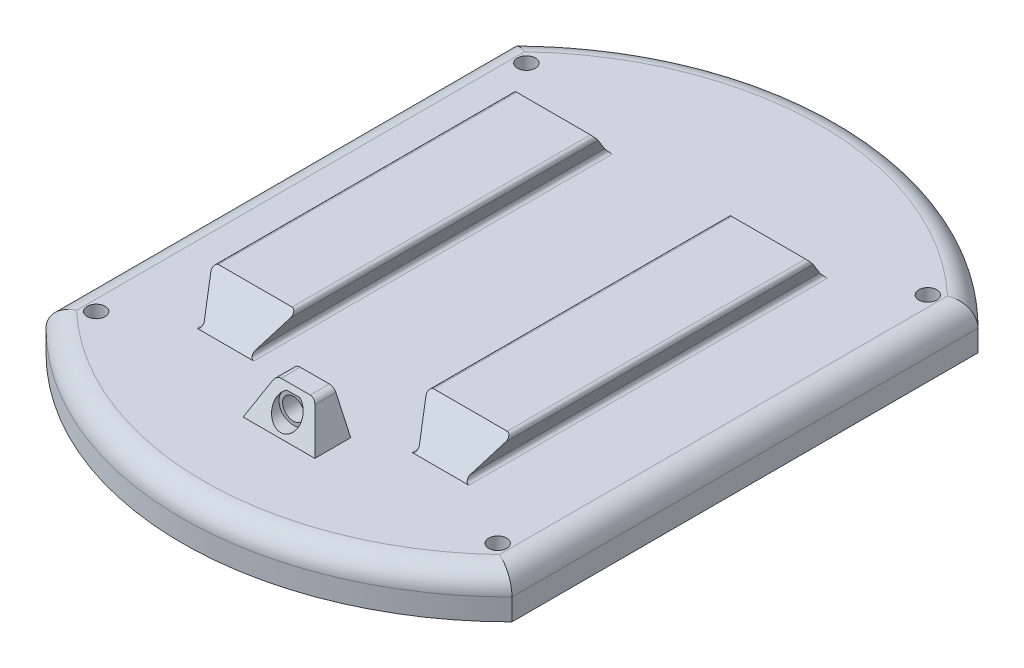
SolidWorks part; units mm, degrees
ref_plane "Спереди" through (0, 0, 0) normal (0, 0, 1) x (1, 0, 0)
ref_plane "Сверху" through (0, 0, 0) normal (0, 1, 0) x (1, 0, 0)
ref_plane "Справа" through (0, 0, 0) normal (1, 0, 0) x (0, 0, -1)
sketch "Эскиз1" plane through (0, 0, 0) normal (0, 1, 0) x (1, 0, 0)
  line L2 (0, -1000) -> (0, 49000) construction
  line L9 (-32.5, -32.5) -> (32.5, -32.5)
  line L10 (-32.5, -32.5) -> (-32.5, 32.5)
  line L11 (-32.5, 32.5) -> (32.5, 32.5)
  line L12 (32.5, -32.5) -> (32.5, 32.5)
  line L13 (-32.5, -32.5) -> (32.5, 32.5) construction
  line L14 (-32.5, 32.5) -> (32.5, -32.5) construction
  arc A5 (32.5, 32.5) -> (-32.5, 32.5) centre (0, 0.1296) ccw
  arc A6 (-32.5, -32.5) -> (32.5, -32.5) centre (0, -0.1296) ccw
  point P17 (0, 0)
  point P26 (0, 46)
  point P28 (0, -46)
  point P29 (0, 0)
  point P30 (0, 0)
  point P49 (0, 0)
  point P50 (-30.25, 31.299)
  point P51 (-28, 27.4019)
  point P52 (-25.75, 28.701)
  point P53 (0, 0)
  point P54 (0, 0)
  point P55 (0, 0)
  dimension "D6" = 65
  dimension "D7" = 92
extrude "Бобышка-Вытянуть1" add sketch "Эскиз1" along normal blind 6 contours L9 L12 L11 L10 | L11 A5 | L9 A6 | L9 | L9 | L11 | L11 | L11 | L11 | L9 | L9 region at (0, 0, 0) region at (0, 0, 37.9745) region at (0, 0, -37.9745)
sketch "Эскиз2" plane through (0, 0, 0) normal (0, -1, 0) x (1, 0, 0)
  line L0 (-25.75, 31.299) -> (-28, 32.5981)
  line L1 (28, 27.4019) -> (30.25, 28.701)
  line L2 (30.25, 28.701) -> (30.25, 31.299)
  line L3 (30.25, 31.299) -> (28, 32.5981)
  line L4 (28, 32.5981) -> (25.75, 31.299)
  line L5 (25.75, 31.299) -> (25.75, 28.701)
  line L6 (25.75, 28.701) -> (28, 27.4019)
  line L7 (-28, 32.5981) -> (-30.25, 31.299)
  line L8 (-30.25, 31.299) -> (-30.25, 28.701)
  line L9 (-30.25, 28.701) -> (-28, 27.4019)
  line L10 (-28, 27.4019) -> (-25.75, 28.701)
  line L11 (-25.75, 28.701) -> (-25.75, 31.299)
  line L12 (-25.75, -28.701) -> (-28, -27.4019)
  line L13 (-28, -27.4019) -> (-30.25, -28.701)
  line L14 (-30.25, -28.701) -> (-30.25, -31.299)
  line L15 (-30.25, -31.299) -> (-28, -32.5981)
  line L16 (-28, -32.5981) -> (-25.75, -31.299)
  line L17 (-25.75, -31.299) -> (-25.75, -28.701)
  line L18 (30.25, -28.701) -> (28, -27.4019)
  line L19 (28, -27.4019) -> (25.75, -28.701)
  line L20 (25.75, -28.701) -> (25.75, -31.299)
  line L21 (25.75, -31.299) -> (28, -32.5981)
  line L22 (28, -32.5981) -> (30.25, -31.299)
  line L23 (30.25, -31.299) -> (30.25, -28.701)
  circle A0 centre (28, 30) radius 2.25 construction
  circle A1 centre (-28, -30) radius 2.5981
  point P9 (0, 0)
  point P10 (0, 0)
  point P29 (0, 0)
  dimension "D1" = 4.5
  dimension "D4" = 28
  dimension "D5" = 30
  dimension "D6" = 28
  dimension "D7" = 30
  dimension "D2" = 2
  dimension "D3" = 2
extrude "Вырез-Вытянуть1" cut sketch "Эскиз2" against normal blind 3 contours L22 L23 L18 L19 L20 L21 | L5 L6 L1 L2 L3 L4 | L10 L11 L0 L7 L8 L9 | L16 L17 L12 L13 L14 L15 | L12 L13 L14 L15 L16 L17 region at (-28, 0, 30) region at (28, 0, 30) region at (-28, 0, -30) region at (28, 0, -30)
sketch "Эскиз3" plane through (0, 6, 0) normal (0, 1, 0) x (1, 0, 0)
  line L0 (-22.5, 28.0659) -> (-22.5, -28.0659)
  line L1 (22.5, -28.0659) -> (22.5, 28.0659)
  line L2 (-32.5, 32.5) -> (-32.5, -32.5)
  line L3 (32.5, -32.5) -> (32.5, 32.5)
  line L4 (-32.5, 32.5) -> (-32.5, -32.5)
  line L5 (32.5, -32.5) -> (32.5, 32.5)
  arc A0 (22.5, 28.0659) -> (-22.5, 28.0659) centre (0, 0.1296) ccw
  arc A1 (-22.5, -28.0659) -> (22.5, -28.0659) centre (0, -0.1296) ccw
  arc A2 (-32.5, -32.5) -> (32.5, -32.5) centre (0, -0.1296) ccw
  arc A3 (32.5, 32.5) -> (-32.5, 32.5) centre (0, 0.1296) ccw
  arc A4 (-32.5, -32.5) -> (32.5, -32.5) centre (0, -0.1296) ccw
  arc A5 (32.5, 32.5) -> (-32.5, 32.5) centre (0, 0.1296) ccw
  dimension "D2" = 10
  dimension "D1" = 0
sketch "Эскиз4" plane through (0, 3, 0) normal (0, -1, 0) x (1, 0, 0)
  line L0 (28, 32.5981) -> (28, 27.4019) construction
  line L1 (28, 27.4019) -> (30.25, 28.701) construction
  line L2 (-32.5, 32.5) -> (-32.5, -32.5)
  line L3 (32.5, -32.5) -> (32.5, 32.5)
  line L4 (-32.5, 32.5) -> (-32.5, -32.5)
  line L5 (32.5, -32.5) -> (32.5, 32.5)
  line L6 (25.75, 28.701) -> (30.25, 31.299) construction
  line L8 (-25.75, -31.299) -> (-25.75, -28.701) construction
  line L9 (-25.75, -30) -> (-28, -30)
  circle A0 centre (28, 30) radius 1.25
  circle A1 centre (-28, 30) radius 1.25
  arc A2 (-32.5, -32.5) -> (32.5, -32.5) centre (0, -0.1296) ccw
  arc A3 (32.5, 32.5) -> (-32.5, 32.5) centre (0, 0.1296) ccw
  arc A4 (-32.5, -32.5) -> (32.5, -32.5) centre (0, -0.1296) ccw
  arc A5 (32.5, 32.5) -> (-32.5, 32.5) centre (0, 0.1296) ccw
  circle A6 centre (-28, -30) radius 1.25
  circle A7 centre (28, -30) radius 1.25
  dimension "D2" = 2.5
  dimension "D1" = 0
  dimension "D3" = 2
  dimension "D4" = 2
extrude "Вырез-Вытянуть3" cut sketch "Эскиз4" against normal through all contours A0 | A1 | A7 | A6 region at (28, 3, 30) region at (-28, 3, 30) region at (-29.2146, 3, -30) region at (28, 3, -30)
sketch "Эскиз5" plane through (0, 0, 0) normal (0, 0, 1) x (1, 0, 0)
  line L0 (0, -1000) -> (0, 49000) construction
  line L1 (9, 11) -> (21, 11)
  line L2 (21, 11) -> (18.1132, 6)
  line L3 (9, 11) -> (11.8868, 6)
  line L4 (-32.5, 0) -> (32.5, 0)
  line L5 (-32.5, 6) -> (-32.5, 0)
  line L6 (32.5, 6) -> (-32.5, 6)
  line L7 (32.5, 0) -> (32.5, 6)
  line L8 (-32.5, 0) -> (32.5, 0)
  line L9 (-32.5, 6) -> (-32.5, 0)
  line L10 (32.5, 6) -> (-32.5, 6)
  line L11 (32.5, 0) -> (32.5, 6)
  line L12 (15, 11) -> (15, 6) construction
  line L13 (-9, 11) -> (-11.8868, 6)
  line L14 (-15, 11) -> (-15, 6) construction
  line L15 (-9, 11) -> (-21, 11)
  line L16 (-21, 11) -> (-18.1132, 6)
  point P13 (15, 8.5)
  dimension "D2" = 60
  dimension "D3" = 5
  dimension "D4" = 12
  dimension "D5" = 15
  dimension "D1" = 0
extrude "Бобышка-Вытянуть2" add sketch "Эскиз5" along normal mid plane 50 contours L15 L16 L10 L13 | L10 L2 L1 L3 region at (15, 8.764, 0) region at (-15, 8.764, 0)
draft "Уклон1" type of draft neutral plane draft angle 40 faces to draft 4 face at (15, 8.5, -25) face at (15, 8.5, 25) face at (-15, 8.5, -25) face at (-15, 8.5, 25) neutral plane through (0, 6, 0) neutral plane normal (0, 1, 0) parameters "D1"=40
fillet "Скругление1" radius 0.5 8 edges at (18.1132, 6, 0) (21, 11, 0) (9, 11, 0) (11.8868, 6, 0) (-11.8868, 6, 0) (-9, 11, 0) (-21, 11, 0) (-18.1132, 6, 0)
sketch "Эскиз6" plane through (0, 6, 0) normal (0, 1, 0) x (1, 0, 0)
  line L1 (-5, -32.5) -> (5, -32.5)
  line L2 (-5, -32.5) -> (-5, -27.5)
  line L3 (-5, -27.5) -> (5, -27.5)
  line L4 (5, -32.5) -> (5, -27.5)
  line L5 (-5, -32.5) -> (5, -27.5) construction
  line L6 (-5, -27.5) -> (5, -32.5) construction
  point P0 (0, -30)
  point P5 (0, 0)
  dimension "D1" = 10
  dimension "D2" = 5
  dimension "D3" = 30
extrude "Бобышка-Вытянуть3" add sketch "Эскиз6" along normal blind 5
draft "Уклон3" type of draft neutral plane draft angle 25 faces to draft 2 face at (5, 8.5, 30) face at (-5, 8.5, 30) neutral plane through (0, 6, 0) neutral plane normal (0, 1, 0) parameters "D1"=25
fillet "Скругление2" radius 1 2 edges at (2.6685, 11, 30) (-2.6685, 11, 30)
sketch "Эскиз7" plane through (0, 0, 32.5) normal (0, 0, 1) x (1, 0, 0)
  line L0 (-2.0314, 11) -> (2.0314, 11) construction
  circle A0 centre (0, 8.5) radius 1.5
  point P4 (0, 0)
  point P5 (0, 0)
  dimension "D1" = 3
  dimension "D2" = 2.5
extrude "Вырез-Вытянуть4" cut sketch "Эскиз7" against normal blind 5
sketch "Эскиз8" plane through (0, 0, 32.5) normal (0, 0, 1) x (1, 0, 0)
  circle A0 centre (0, 8.5) radius 1.5 construction
  circle A1 centre (0, 8.5) radius 1.5
  circle A2 centre (0, 8.5) radius 2
  dimension "D1" = 4
extrude "Вырез-Вытянуть5" cut sketch "Эскиз8" against normal blind 2
draft "Уклон5" type of draft neutral plane draft angle 25 faces to draft 1 face at (2, 8.5, 32.5) neutral plane through (0, 6, 0) neutral plane normal (0, 1, 0) parameters "D1"=25
fillet "Скругление3" radius 3 4 edges at (0, 6, 46) (-32.5, 6, 0) (32.5, 6, 0) (0, 6, -46)
